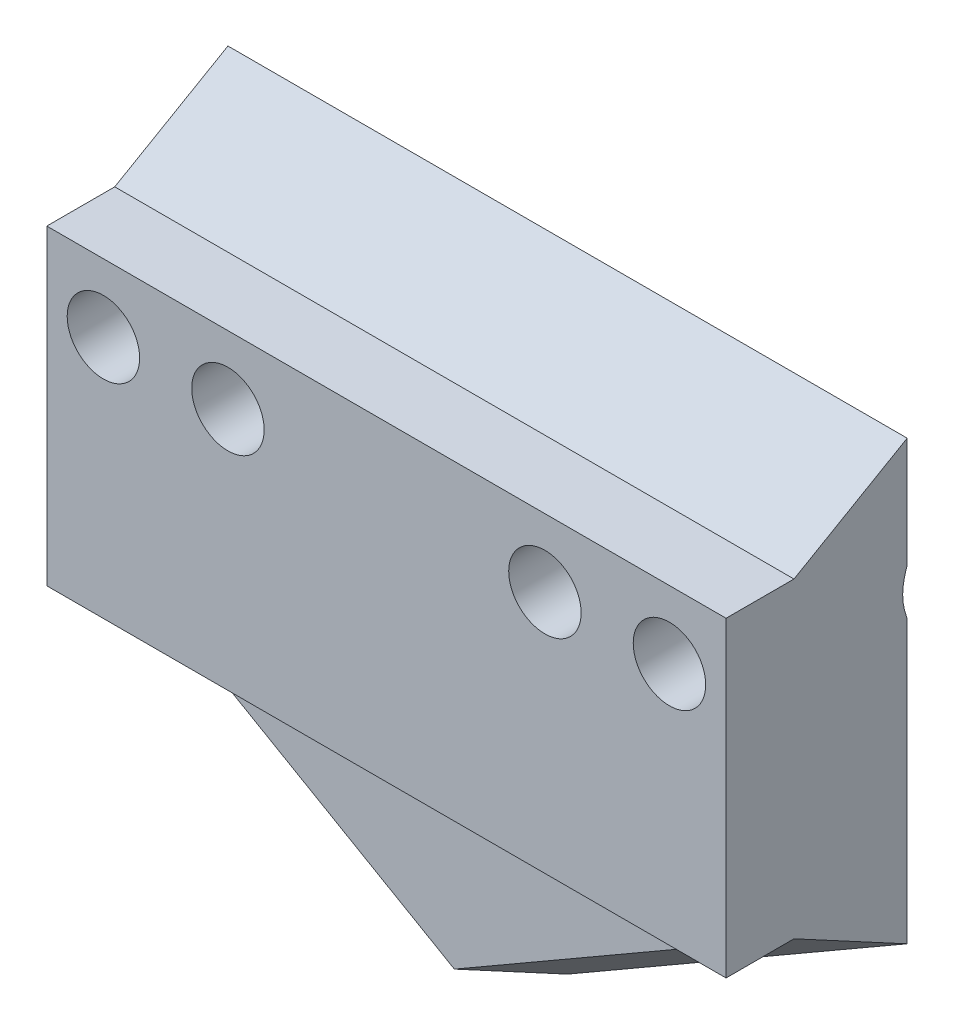
SolidWorks part; units mm, degrees
ref_plane "Plano frontal" through (0, 0, 0) normal (0, 0, 1) x (1, 0, 0)
ref_plane "Plano superior" through (0, 0, 0) normal (0, 1, 0) x (1, 0, 0)
ref_plane "Plano direito" through (0, 0, 0) normal (1, 0, 0) x (0, 0, -1)
sketch "Esboço1" plane through (0, 0, 0) normal (0, 0, 1) x (1, 0, 0)
  line L0 (-15, 28) -> (-15, 8.6603)
  line L1 (-15, 8.6603) -> (0, 0)
  line L2 (0, 0) -> (0, 28) construction
  line L3 (15, 28) -> (-15, 28)
  line L4 (15, 8.6603) -> (0, 0)
  line L5 (15, 28) -> (15, 8.6603)
  dimension "D1" = 120
  dimension "D2" = 30
  dimension "D3" = 28
extrude "Ressalto-extrusão1" add sketch "Esboço1" along normal blind 5
chamfer "Chanfro1" distance 5 angle 25 2 edges at (-7.5, 4.3301, 5) (7.5, 4.3301, 5) first distance on face at (-7.5, 4.3301, 2.5) first distance on face at (7.5, 4.3301, 2.5)
chamfer "Chanfro2" distance 5 angle 30 1 edges at (0, 28, 5) first distance on face at (0, 28, 2.5)
sketch "Esboço2" plane through (0, 0, 5) normal (0, 0, 1) x (1, 0, 0)
  line L0 (15, 25.1132) -> (-15, 25.1132) construction
  line L1 (-15, 11.3525) -> (15, 11.3525)
  line L2 (-15, 11.3525) -> (-15, 25.1132)
  line L3 (-15, 25.1132) -> (15, 25.1132)
  line L4 (15, 11.3525) -> (15, 25.1132)
  line L5 (-15, 11.3525) -> (15, 25.1132) construction
  line L6 (-15, 25.1132) -> (15, 11.3525) construction
  line L7 (0, 2.6922) -> (15, 11.3525) construction
  point P0 (0, 18.2329)
  dimension "D1" = 30
extrude "Ressalto-extrusão2" add sketch "Esboço2" along normal blind 3
sketch "Esboço3" plane through (0, 0, 0) normal (0, 0, 1) x (1, 0, 0)
  line L0 (0, 0) -> (0, 25.7319) construction
  line L2 (15, 25.1132) -> (-15, 25.1132) construction
  circle A0 centre (-7, 22.1132) radius 1.6
  circle A1 centre (7, 22.1132) radius 1.6
  circle A2 centre (-12.5, 22.1132) radius 1.6
  circle A3 centre (12.5, 22.1132) radius 1.6
  point P13 (0, 0)
  dimension "D2" = 3.2
  dimension "D1" = 14
  dimension "D3" = 3
  dimension "D4" = 25
extrude "Corte-extrusão1" cut sketch "Esboço3" along normal through all both and the other way through all
sketch "Esboço4" plane through (0, 0, 0) normal (0, 0, -1) x (-1, 0, 0)
  line L0 (0, 0) -> (0, 23.2948) construction
  line L1 (-7, 18.8801) -> (-4.2, 20.4967)
  line L2 (-4.2, 20.4967) -> (-4.2, 23.7298)
  line L3 (-4.2, 23.7298) -> (-7, 25.3464)
  line L4 (-7, 25.3464) -> (-9.8, 23.7298)
  line L5 (-9.8, 23.7298) -> (-9.8, 20.4967)
  line L6 (-9.8, 20.4967) -> (-7, 18.8801)
  line L7 (9.8, 20.4967) -> (7, 18.8801)
  line L8 (9.8, 23.7298) -> (9.8, 20.4967)
  line L9 (7, 25.3464) -> (9.8, 23.7298)
  line L10 (4.2, 23.7298) -> (7, 25.3464)
  line L11 (4.2, 20.4967) -> (4.2, 23.7298)
  line L12 (7, 18.8801) -> (4.2, 20.4967)
  circle A2 centre (-7, 22.1132) radius 2.8 construction
  circle A3 centre (7, 22.1132) radius 2.8 construction
  circle A4 centre (12.5, 22.1132) radius 2
  circle A5 centre (-12.5, 22.1132) radius 2
  dimension "D1" = 5.6
  dimension "D2" = 4
extrude "Corte-extrusão2" cut sketch "Esboço4" against normal blind 2
sketch "Esboço6" plane through (0, 0, 0) normal (0, 0, -1) x (-1, 0, 0)
  line L1 (-2.25, 20) -> (2.25, 20)
  line L2 (-2.25, 20) -> (-2.25, 5)
  line L3 (-2.25, 5) -> (2.25, 5)
  line L4 (2.25, 20) -> (2.25, 5)
  line L5 (-2.25, 20) -> (2.25, 5) construction
  line L6 (-2.25, 5) -> (2.25, 20) construction
  point P0 (0, 12.5)
  point P5 (0.7499, 12.9641)
  dimension "D1" = 4.5
  dimension "D2" = 15
  dimension "D3" = 5
extrude "Corte-extrusão3" cut sketch "Esboço6" against normal blind 4
extrude "Corte-extrusão4" cut sketch "Esboço4<2>" against normal blind 4 contours A5 | A4
sketch "Esboço4<2>" plane through (0, 0, 0) normal (0, 0, -1) x (-1, 0, 0) same geometry as "Esboço4"
chamfer "Chanfro3" distance 0.7 angle 45 2 edges at (-14.5, 22.1132, 0) (10.5, 22.1132, 0)
